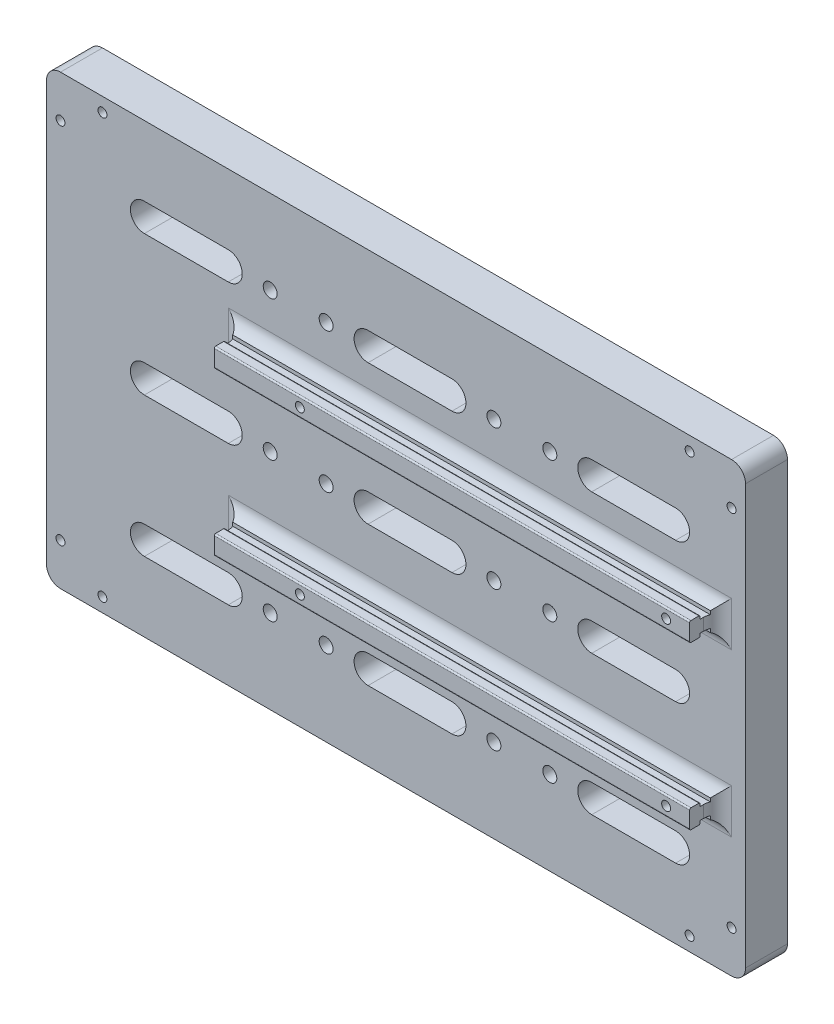
SolidWorks part; units mm, degrees
ref_plane "前视基准面" through (0, 0, 0) normal (0, 0, 1) x (1, 0, 0)
ref_plane "上视基准面" through (0, 0, 0) normal (0, 1, 0) x (1, 0, 0)
ref_plane "右视基准面" through (0, 0, 0) normal (1, 0, 0) x (0, 0, -1)
other "Configuration Table"
sketch "草图1" plane through (0, 0, 0) normal (0, 0, 1) x (1, 0, 0)
  line L0 (0, 0) -> (0, 26371.7997) construction
  line L1 (0, 0) -> (26371.7997, 0) construction
  line L3 (-125, 80) -> (125, 80)
  line L4 (-125, 80) -> (-125, -80)
  line L5 (-125, -80) -> (125, -80)
  line L6 (125, 80) -> (125, -80)
  line L7 (-125, 80) -> (125, -80) construction
  line L8 (-125, -80) -> (125, 80) construction
  point P5 (0, 0)
  dimension "D1" = 250
  dimension "D2" = 160
extrude "凸台-拉伸1" add sketch "草图1" along normal blind 15
sketch "草图2" plane through (0, 0, 15) normal (0, 0, 1) x (1, 0, 0)
  line L0 (0, 0) -> (50000, 0) construction
  line L1 (0, 0) -> (0, 50000) construction
  line L2 (125, -80) -> (125, 80) construction
  line L3 (-55, 32.4) -> (115, 32.4)
  line L4 (-55, 32.4) -> (-55, 25.6)
  line L5 (-55, 25.6) -> (115, 25.6)
  line L6 (115, 32.4) -> (115, 25.6)
  line L7 (-55, 32.4) -> (115, 25.6) construction
  line L8 (-55, 25.6) -> (115, 32.4) construction
  line L9 (-55, -25.6) -> (115, -25.6)
  line L10 (115, -32.4) -> (115, -25.6)
  line L11 (-55, -32.4) -> (-55, -25.6)
  line L12 (-55, -32.4) -> (115, -32.4)
  point P5 (30, 29)
  dimension "D1" = 29
  dimension "D2" = 170
  dimension "D3" = 10
  dimension "D4" = 6.8
extrude "凸台-拉伸2" add sketch "草图2" along normal blind 10
sketch "草图3" plane through (115, 0, 0) normal (1, 0, 0) x (0, 0, -1)
  line L0 (-25, 29) -> (-15, 29) construction
  line L1 (-25, 25.6) -> (-25, 32.4) construction
  line L2 (-15, 25.6) -> (-15, 32.4) construction
  line L3 (-25, 32.4) -> (-15, 32.4) construction
  line L4 (-21.2, 32.4) -> (-18, 32.4)
  line L5 (-21.2, 32.4) -> (-21.2, 31.15)
  line L6 (-21.2, 31.15) -> (-18, 31.15)
  line L7 (-18, 32.4) -> (-18, 31.15)
  line L8 (-21.2, 26.85) -> (-18, 26.85)
  line L9 (-18, 25.6) -> (-18, 26.85)
  line L10 (-21.2, 25.6) -> (-21.2, 26.85)
  line L11 (-21.2, 25.6) -> (-18, 25.6)
  dimension "D1" = 3.8
  dimension "D2" = 3.2
  dimension "D3" = 4.3
extrude "切除-拉伸1" cut sketch "草图3" against normal through all
fillet "圆角1" radius 0.5 4 edges at (30, 25.6, 21.2) (30, 25.6, 25) (30, 32.4, 25) (30, 32.4, 21.2)
sketch "草图4" plane through (115, 0, 0) normal (1, 0, 0) x (0, 0, -1)
  line L0 (-25, -29) -> (-15, -29) construction
  line L1 (-25, -32.4) -> (-25, -25.6) construction
  line L2 (-15, -32.4) -> (-15, -25.6) construction
  line L3 (-25, -25.6) -> (-15, -25.6) construction
  line L4 (-21.2, -25.6) -> (-18, -25.6)
  line L5 (-21.2, -25.6) -> (-21.2, -26.85)
  line L6 (-21.2, -26.85) -> (-18, -26.85)
  line L7 (-18, -25.6) -> (-18, -26.85)
  line L8 (-18, -32.4) -> (-18, -31.15)
  line L9 (-21.2, -31.15) -> (-18, -31.15)
  line L10 (-21.2, -32.4) -> (-21.2, -31.15)
  line L11 (-21.2, -32.4) -> (-18, -32.4)
  dimension "D1" = 3.8
  dimension "D2" = 3.2
  dimension "D3" = 4.3
extrude "切除-拉伸2" cut sketch "草图4" against normal through all
fillet "圆角2" radius 0.5 4 edges at (30, -32.4, 21.2) (30, -32.4, 25) (30, -25.6, 25) (30, -25.6, 21.2)
fillet "圆角3" radius 5 2 edges at (30, 25.6, 15) (30, 32.4, 15)
fillet "圆角4" radius 5 2 edges at (115, 29, 15) (-55, 29, 15)
fillet "圆角5" radius 5 4 edges at (-55, -29, 15) (115, -29, 15) (30, -25.6, 15) (30, -32.4, 15)
sketch "草图5" plane through (0, 0, 0) normal (0, 0, -1) x (-1, 0, 0)
  line L0 (-125, 0) -> (131.1555, 0) construction
  line L1 (-125, -80) -> (-125, 80) construction
  line L2 (-30, 29) -> (-115, 29) construction
  line L3 (-115, 32.4) -> (-115, 25.6) construction
  line L4 (-115, 29) -> (55, 29) construction
  line L5 (55, 32.4) -> (55, 25.6) construction
  circle A0 centre (-106.6, 29) radius 1.6
  circle A1 centre (24.4, 29) radius 1.6
  circle A2 centre (24.4, -29) radius 1.6
  circle A3 centre (-106.6, -29) radius 1.6
  dimension "D1" = 8.4
  dimension "D2" = 3.2
  dimension "D3" = 3.2
  dimension "D4" = 131
extrude "切除-拉伸3" cut sketch "草图5" against normal through all
sketch "草图6" plane through (0, 0, 0) normal (0, 0, -1) x (-1, 0, 0)
  line L0 (-125, 80) -> (-95, 80)
  line L1 (-125, 80) -> (125, 80) construction
  line L2 (-95, 80) -> (-95, 70)
  line L3 (-95, 70) -> (-115, 70)
  line L4 (-115, 70) -> (-115, 60)
  line L5 (-115, 60) -> (-125, 60)
  line L6 (-125, -80) -> (-125, 80) construction
  line L7 (-125, 60) -> (-125, 80)
  line L8 (0, 0) -> (50000, 0) construction
  line L9 (125, 80) -> (95, 80)
  line L10 (95, 80) -> (95, 70)
  line L11 (95, 70) -> (115, 70)
  line L12 (115, 70) -> (115, 60)
  line L13 (115, 60) -> (125, 60)
  line L14 (125, 80) -> (125, -80) construction
  line L15 (125, 60) -> (125, 80)
  line L16 (-125, -60) -> (-125, -80)
  line L17 (-115, -60) -> (-125, -60)
  line L18 (-115, -70) -> (-115, -60)
  line L19 (-95, -70) -> (-115, -70)
  line L20 (-95, -80) -> (-95, -70)
  line L21 (-125, -80) -> (-95, -80)
  line L22 (125, -60) -> (125, -80)
  line L23 (115, -60) -> (125, -60)
  line L24 (115, -70) -> (115, -60)
  line L25 (95, -70) -> (115, -70)
  line L26 (95, -80) -> (95, -70)
  line L27 (125, -80) -> (95, -80)
  circle A0 centre (-120, 65) radius 1.6
  circle A1 centre (-105, 75) radius 1.6
  circle A2 centre (105, 75) radius 1.6
  circle A3 centre (120, 65) radius 1.6
  circle A4 centre (120, -65) radius 1.6
  circle A5 centre (105, -75) radius 1.6
  circle A6 centre (-105, -75) radius 1.6
  circle A7 centre (-120, -65) radius 1.6
  dimension "D9" = 3.2
  dimension "D10" = 5
  dimension "D11" = 5
  dimension "D12" = 3.2
  dimension "D13" = 5
  dimension "D14" = 10
  dimension "D15" = 5
  dimension "D16" = 10
  dimension "D17" = 3.2
  dimension "D18" = 5
  dimension "D19" = 5
  dimension "D20" = 3.2
  dimension "D1" = 30
  dimension "D2" = 20
  dimension "D3" = 10
  dimension "D4" = 10
  dimension "D5" = 30
  dimension "D6" = 20
  dimension "D7" = 10
  dimension "D8" = 10
extrude "切除-拉伸4" cut sketch "草图6" against normal through all contours A5 | A4 | A3 | A2 | A1 | A0 | A7 | A6
sketch "草图8" plane through (0, 0, 0) normal (0, 0, -1) x (-1, 0, 0)
  line L0 (-20, 5) -> (10, 5)
  line L5 (-200000, 0) -> (250000, 0) construction
  line L6 (-100, 5) -> (-70, 5)
  line L7 (-100, 5) -> (-100, -5) construction
  line L8 (-100, -5) -> (-70, -5)
  line L9 (-70, 5) -> (-70, -5) construction
  line L10 (-100, 5) -> (-70, -5) construction
  line L11 (-100, -5) -> (-70, 5) construction
  line L12 (-125, -80) -> (-125, 80) construction
  line L13 (-20, -5) -> (10, -5)
  line L14 (-20, 5) -> (-20, -5) construction
  line L15 (10, 5) -> (10, -5) construction
  line L16 (-20, 5) -> (10, -5) construction
  line L17 (-20, -5) -> (10, 5) construction
  line L18 (60, 5) -> (90, 5)
  line L19 (60, -5) -> (90, -5)
  line L20 (60, 5) -> (60, -5) construction
  line L21 (90, 5) -> (90, -5) construction
  line L22 (60, 5) -> (90, -5) construction
  line L23 (60, -5) -> (90, 5) construction
  line L24 (-20, 55) -> (10, 55)
  line L25 (-100, 55) -> (-70, 55)
  line L26 (-100, 45) -> (-70, 45)
  line L27 (-20, 45) -> (10, 45)
  line L28 (60, 55) -> (90, 55)
  line L29 (60, 45) -> (90, 45)
  line L30 (-100, 55) -> (-100, 45) construction
  line L31 (-70, 55) -> (-70, 45) construction
  line L32 (-100, 55) -> (-70, 45) construction
  line L33 (-100, 45) -> (-70, 55) construction
  line L34 (-20, 55) -> (-20, 45) construction
  line L35 (10, 55) -> (10, 45) construction
  line L36 (-20, 55) -> (10, 45) construction
  line L37 (-20, 45) -> (10, 55) construction
  line L38 (60, 55) -> (60, 45) construction
  line L39 (90, 55) -> (90, 45) construction
  line L40 (60, 55) -> (90, 45) construction
  line L41 (60, 45) -> (90, 55) construction
  line L42 (-20, -45) -> (10, -45)
  line L43 (-100, -45) -> (-70, -45)
  line L44 (-100, -55) -> (-70, -55)
  line L45 (-20, -55) -> (10, -55)
  line L46 (60, -45) -> (90, -45)
  line L47 (60, -55) -> (90, -55)
  line L48 (-100, -45) -> (-100, -55) construction
  line L49 (-70, -45) -> (-70, -55) construction
  line L50 (-100, -45) -> (-70, -55) construction
  line L51 (-100, -55) -> (-70, -45) construction
  line L52 (-20, -45) -> (-20, -55) construction
  line L53 (10, -45) -> (10, -55) construction
  line L54 (-20, -45) -> (10, -55) construction
  line L55 (-20, -55) -> (10, -45) construction
  line L56 (60, -45) -> (60, -55) construction
  line L57 (90, -45) -> (90, -55) construction
  line L58 (60, -45) -> (90, -55) construction
  line L59 (60, -55) -> (90, -45) construction
  arc A0 (-100, -5) -> (-100, 5) centre (-100, 0) cw
  arc A1 (-70, -5) -> (-70, 5) centre (-70, 0) ccw
  arc A2 (-20, -5) -> (-20, 5) centre (-20, 0) cw
  arc A3 (10, -5) -> (10, 5) centre (10, 0) ccw
  arc A4 (60, -5) -> (60, 5) centre (60, 0) cw
  arc A5 (90, -5) -> (90, 5) centre (90, 0) ccw
  arc A6 (-100, 45) -> (-100, 55) centre (-100, 50) cw
  arc A7 (-70, 45) -> (-70, 55) centre (-70, 50) ccw
  arc A8 (-20, 45) -> (-20, 55) centre (-20, 50) cw
  arc A9 (10, 45) -> (10, 55) centre (10, 50) ccw
  arc A10 (60, 45) -> (60, 55) centre (60, 50) cw
  arc A11 (90, 45) -> (90, 55) centre (90, 50) ccw
  arc A12 (-100, -55) -> (-100, -45) centre (-100, -50) cw
  arc A13 (-70, -55) -> (-70, -45) centre (-70, -50) ccw
  arc A14 (-20, -55) -> (-20, -45) centre (-20, -50) cw
  arc A15 (10, -55) -> (10, -45) centre (10, -50) ccw
  arc A16 (60, -55) -> (60, -45) centre (60, -50) cw
  arc A17 (90, -55) -> (90, -45) centre (90, -50) ccw
  circle A18 centre (-55, 0) radius 2.5
  circle A19 centre (-35, 0) radius 2.5
  circle A20 centre (25, 0) radius 2.5
  circle A21 centre (45, 0) radius 2.5
  circle A22 centre (-55, 50) radius 2.5
  circle A23 centre (-35, 50) radius 2.5
  circle A24 centre (25, 50) radius 2.5
  circle A25 centre (45, 50) radius 2.5
  circle A26 centre (-55, -50) radius 2.5
  circle A27 centre (-35, -50) radius 2.5
  circle A28 centre (25, -50) radius 2.5
  circle A29 centre (45, -50) radius 2.5
  point P0 (-85, 0)
  point P13 (-5, 0)
  point P20 (75, 0)
  point P27 (-85, 50)
  point P34 (-5, 50)
  point P41 (75, 50)
  point P48 (-85, -50)
  point P55 (-5, -50)
  point P62 (75, -50)
  dimension "D7" = 5
  dimension "D8" = 15
  dimension "D9" = 5
  dimension "D10" = 15
  dimension "D11" = 20
  dimension "D1" = 10
  dimension "D2" = 30
  dimension "D3" = 40
  dimension "D4" = 3
  dimension "D5" = 2
  dimension "D6" = 2
  dimension "D12" = 2
  dimension "D13" = 2
  dimension "D14" = 2
extrude "切除-拉伸5" cut sketch "草图8" against normal through all
fillet "圆角6" radius 5 4 edges at (-125, 80, 7.5) (125, 80, 7.5) (125, -80, 7.5) (-125, -80, 7.5)
sketch "草图9" plane through (0, 0, 0) normal (0, 0, -1) x (-1, 0, 0)
  circle A0 centre (-106.6, 29) radius 3
  circle A1 centre (24.4, 29) radius 3
  circle A2 centre (-106.6, -29) radius 3
  circle A3 centre (24.4, -29) radius 3
  dimension "D1" = 6
  dimension "D2" = 6
  dimension "D3" = 6
  dimension "D4" = 6
extrude "切除-拉伸6" cut sketch "草图9" against normal blind 3
